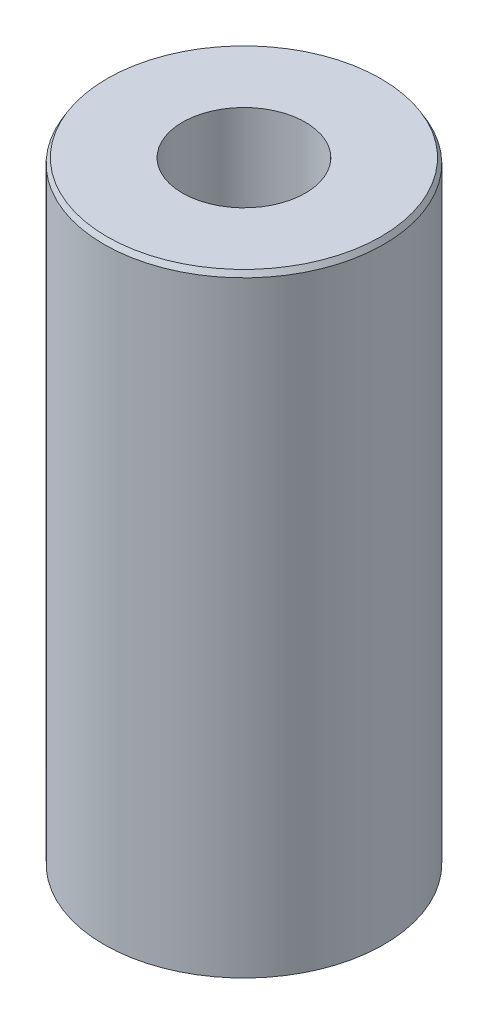
SolidWorks part; units mm, degrees
ref_plane "Front Plane" through (0, 0, 0) normal (0, 0, 1) x (1, 0, 0)
ref_plane "Top Plane" through (0, 0, 0) normal (0, 1, 0) x (1, 0, 0)
ref_plane "Right Plane" through (0, 0, 0) normal (1, 0, 0) x (0, 0, -1)
sketch "Sketch1" plane through (0, 0, 0) normal (0, 1, 0) x (1, 0, 0)
  circle A0 centre (0, 0) radius 15
  dimension "SHAFT_OD" = 30
extrude "Boss-Extrude1" add sketch "Sketch1" along normal blind 65.895
sketch "Sketch2" plane through (0, 0, 0) normal (0, 1, 0) x (1, 0, 0)
  circle A0 centre (0, 0) radius 6.5907
  dimension "BORE_D" = 13.1815
extrude "Cut-Extrude1" cut sketch "Sketch2" along normal through all
chamfer "Chamfer1" distance 0.5555 angle 30 2 edges at (0, 65.895, 15) (0, 0, 15) first distance on face at (0, 65.895, 15) first distance on face at (0, 0, 6.5907)
